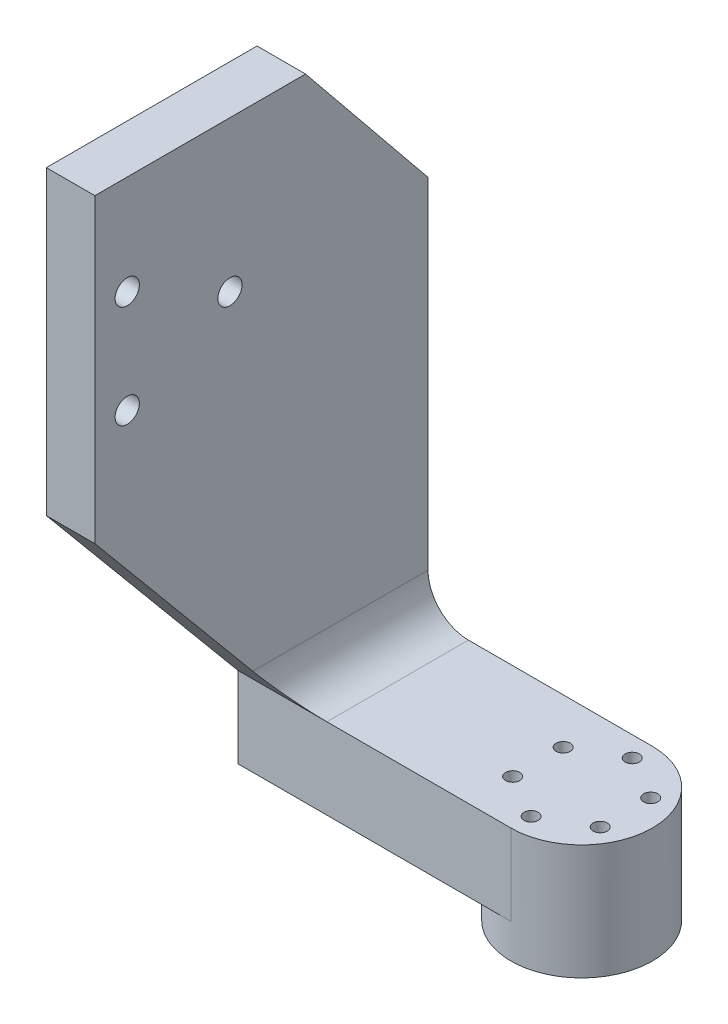
SolidWorks part; units mm, degrees
material "PLA"
ref_plane "Front Plane" through (0, 0, 0) normal (0, 0, 1) x (1, 0, 0)
ref_plane "Top Plane" through (0, 0, 0) normal (0, 1, 0) x (1, 0, 0)
ref_plane "Right Plane" through (0, 0, 0) normal (1, 0, 0) x (0, 0, -1)
sketch "Sketch1" plane through (0, 0, 0) normal (0, 1, 0) x (1, 0, 0)
  line L0 (0, 17.5) -> (67.5, 17.5)
  line L1 (0, -17.5) -> (67.5, -17.5)
  line L2 (67.5, -17.5) -> (67.5, 17.5)
  circle A0 centre (0, 0) radius 17.5
  dimension "D1" = 35
  dimension "D2" = 67.5
extrude "Boss-Extrude1" add sketch "Sketch1" along normal blind 20 contours A0 | A0 L1 L2 L0 region at (40.4803, 0, 0) region at (0, 0, 0)
sketch "Sketch2" plane through (0, 0, 0) normal (0, -1, 0) x (1, 0, 0)
  circle A0 centre (0, 0) radius 17.5 construction
  circle A1 centre (0, 0) radius 17.5
extrude "Boss-Extrude2" add sketch "Sketch2" along normal blind 8.5
sketch "Sketch3" plane through (67.5, 0, 0) normal (1, 0, 0) x (0, 0, -1)
  line L0 (17.5, 0) -> (17.5, 20)
  line L1 (-17.5, 20) -> (-57.39, 67.85)
  line L2 (17.5, 20) -> (17.5, 67.85) construction
  line L3 (17.5, 67.85) -> (-57.39, 67.85) construction
  line L4 (17.5, 20) -> (-12.79, 67.85) construction
  line L5 (-12.79, 67.85) -> (-57.39, 67.85)
  line L6 (17.5, 0) -> (-17.5, 0)
  line L7 (-17.5, 0) -> (17.5, 0) construction
  line L8 (-17.5, 0) -> (-17.5, 20)
  line L9 (-57.39, 67.85) -> (-64.89, 76.8466)
  line L10 (-57.39, 67.85) -> (-64.89, 67.85)
  line L11 (-64.89, 76.8466) -> (-64.89, 151.39)
  line L12 (-64.89, 151.39) -> (-12.79, 151.39)
  line L13 (-12.79, 151.39) -> (-12.79, 67.85) construction
  line L14 (17.5, 20) -> (17.5, 114.1183)
  line L15 (-12.79, 151.39) -> (17.5, 114.1183)
  point P19 (-64.89, 114.1183)
  line M1 (-17.5, 0) -> (17.5, 0)
  line M2 (17.5, 0) -> (17.5, 20)
  line M3 (17.5, 20) -> (-17.5, 20)
  line M4 (-17.5, 20) -> (-17.5, 0)
  dimension "D1" = 47.85
  dimension "D2" = 74.89
  dimension "D3" = 30.29
  dimension "D4" = 7.5
  dimension "D5" = 83.54
extrude "Boss-Extrude3" add sketch "Sketch3" against normal blind 12 contours L13 L12 L11 L9 L5 | L4 L5 L1 M3 | M4 M1 M2 M3 region at (67.5, 10, 0) region at (67.5, 89.3854, 21.8264)
sketch "Sketch4" plane through (67.5, 0, 0) normal (1, 0, 0) x (0, 0, -1)
  line L0 (-56.89, 126.8183) -> (-56.89, 101.4183) construction
  line L1 (-64.89, 76.8466) -> (-64.89, 151.39) construction
  line L2 (-56.89, 114.1183) -> (-31.49, 114.1183) construction
  circle A0 centre (-56.89, 101.4183) radius 3
  circle A1 centre (-56.89, 126.8183) radius 3
  circle A2 centre (-31.49, 114.1183) radius 3
  point P4 (-64.89, 114.1183)
  point P5 (-56.89, 114.1183)
  dimension "D3" = 6
  dimension "D4" = 6
  dimension "D6" = 6
  dimension "D1" = 25.4
  dimension "D2" = 8
  dimension "D5" = 25.4
extrude "Cut-Extrude1" cut sketch "Sketch4" against normal through all
sketch "Sketch5" plane through (0, -8.5, 0) normal (0, -1, 0) x (1, 0, 0)
  line L0 (0, 0) -> (0, 12.5) construction
  circle A0 centre (0, 12.5) radius 1.75
  circle A1 centre (10.8253, 6.25) radius 1.75
  circle A2 centre (10.8253, -6.25) radius 1.75
  circle A3 centre (0, -12.5) radius 1.75
  circle A4 centre (-10.8253, -6.25) radius 1.75
  circle A5 centre (-10.8253, 6.25) radius 1.75
  point P16 (0, 0)
  dimension "D2" = 3.5
  dimension "D1" = 12.5
  dimension "D3" = 6
extrude "Cut-Extrude2" cut sketch "Sketch5" against normal through all
fillet "Fillet1" radius 10 1 edges at (55.5, 20, 0)
ref_plane "Plane1" through (-20, 0, 0) normal (1, 0, 0) x (0, 0, -1)
mirror "Mirror1" about plane through (-20, 0, 0) normal (1, 0, 0) of bodies 105
delete or keep bodies "Body-Delete/Keep 1" type delete bodies bodies 105
